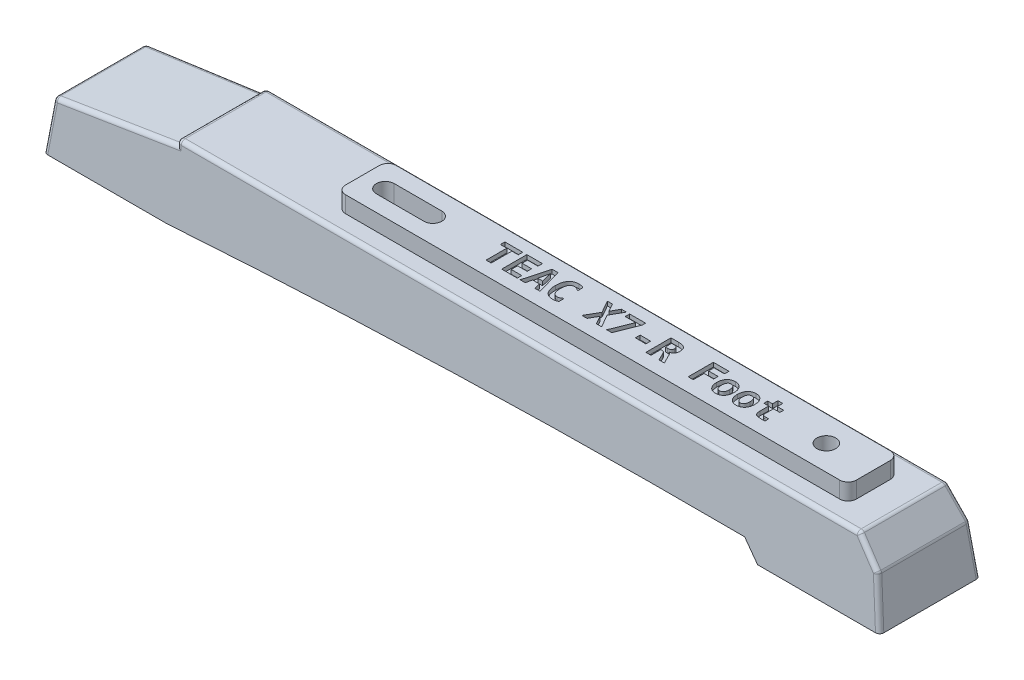
SolidWorks part; units mm, degrees
ref_plane "Front Plane" through (0, 0, 0) normal (0, 0, 1) x (1, 0, 0)
ref_plane "Top Plane" through (0, 0, 0) normal (0, 1, 0) x (1, 0, 0)
ref_plane "Right Plane" through (0, 0, 0) normal (1, 0, 0) x (0, 0, -1)
sketch "Sketch1" plane through (0, 0, 0) normal (0, 1, 0) x (1, 0, 0)
  line L0 (-116.43, -6.1009) -> (-105.07, -6.1009) construction
  line L1 (-2, 0) -> (-119.93, 0)
  line L2 (0, -2) -> (0, -10.09)
  line L3 (-2, -12.09) -> (-119.93, -12.09)
  line L4 (-121.93, -2) -> (-121.93, -10.09)
  line L5 (-116.43, -3.9759) -> (-105.07, -3.9759)
  line L6 (-116.43, -8.2259) -> (-105.07, -8.2259)
  line L8 (-6.38, -2.95) -> (-2.48, -2.95)
  line L9 (-6.38, -2.95) -> (-6.38, -9.14)
  line L10 (-6.38, -9.14) -> (-2.48, -9.14)
  line L11 (-2.48, -2.95) -> (-2.48, -9.14)
  line L12 (-118.88, -1.42) -> (-102.67, -1.42)
  line L13 (-118.88, -1.42) -> (-118.88, -2.6)
  line L14 (-118.88, -2.6) -> (-102.67, -2.6)
  line L15 (-102.67, -1.42) -> (-102.67, -2.6)
  line L16 (-118.88, -9.52) -> (-102.67, -9.52)
  line L17 (-118.88, -9.52) -> (-118.88, -10.7)
  line L18 (-118.88, -10.7) -> (-102.67, -10.7)
  line L19 (-102.67, -9.52) -> (-102.67, -10.7)
  circle A0 centre (-11.18, -6.1009) radius 2.235
  arc A1 (-116.43, -3.9759) -> (-116.43, -8.2259) centre (-116.43, -6.1009) ccw
  arc A2 (-105.07, -8.2259) -> (-105.07, -3.9759) centre (-105.07, -6.1009) ccw
  arc A3 (-119.93, -12.09) -> (-121.93, -10.09) centre (-119.93, -10.09) cw
  arc A4 (-119.93, 0) -> (-121.93, -2) centre (-119.93, -2) ccw
  arc A5 (0, -10.09) -> (-2, -12.09) centre (-2, -10.09) cw
  arc A6 (-2, 0) -> (0, -2) centre (-2, -2) cw
  point P9 (-110.75, -6.1009)
  point P22 (-121.93, 0)
  point P25 (0, -12.09)
  point P28 (0, 0)
  dimension "D3" = 6.1009
  dimension "D4" = 5.5
  dimension "D9" = 4.47
  dimension "D11" = 2
  dimension "D13" = 11.36
  dimension "D1" = 12.09
  dimension "D2" = 121.93
  dimension "D5" = 11.18
  dimension "D6" = 3.9
  dimension "D7" = 6.19
  dimension "D8" = 2.95
  dimension "D10" = 2.48
  dimension "D12" = 4.25
  dimension "D14" = 1.18
  dimension "D15" = 1.18
  dimension "D16" = 1.39
  dimension "D17" = 1.42
  dimension "D18" = 3.05
  dimension "D19" = 3.05
  dimension "D20" = 16.21
extrude "Boss-Extrude1" add sketch "Sketch1" along normal blind 3.93 contours L15 L12 L13 L14 | A6 L1 A4 L4 A3 L3 A5 L2 A2 L6 A1 L5 A0 L8 L11 L10 L9 L12 L15 L14 L13 L16 L19 L18 L17 | L19 L16 L17 L18 | L11 L8 L9 L10 region at (-58.8079, 0, 6.0413) region at (-4.43, 0, 6.045) region at (-110.775, 0, 2.01) region at (-110.775, 0, 10.11)
sketch "Sketch2" plane through (0, 0, 0) normal (0, -1, 0) x (1, 0, 0)
  line L0 (-2, 0) -> (-119.93, 0) construction
  line L1 (13.52, 18.07) -> (-186.01, 18.07)
  line L2 (13.52, 18.07) -> (13.52, -5.98)
  line L3 (13.52, -5.98) -> (-186.01, -5.98)
  line L4 (-186.01, 18.07) -> (-186.01, -5.98)
  line L5 (0, 2) -> (0, 10.09) construction
  line L6 (-121.93, 2) -> (-121.93, 10.09) construction
  dimension "D1" = 24.05
  dimension "D2" = 5.98
  dimension "D3" = 13.52
  dimension "D4" = 64.08
extrude "Boss-Extrude2" add sketch "Sketch2" along normal blind 17.4
sketch "Sketch3" plane through (0, 0, 18.07) normal (0, 0, 1) x (1, 0, 0)
  line L0 (13.52, -17.4) -> (12.04, -5.98)
  line L1 (12.04, -5.98) -> (7.2, 0)
  line L2 (13.52, 0) -> (-186.01, 0) construction
  line L3 (7.2, 0) -> (13.52, 0)
  line L4 (13.52, 0) -> (13.52, -17.4)
  line L5 (13.52, -17.4) -> (-186.01, -17.4) construction
  line L6 (0, 3.93) -> (0, 0) construction
  dimension "D1" = 11.42
  dimension "D2" = 7.2
  dimension "D3" = 1.48
extrude "Cut-Extrude1" cut sketch "Sketch3" against normal through all
sketch "Sketch5" plane through (0, 0, 18.07) normal (0, 0, 1) x (1, 0, 0)
  line L0 (-186.01, -17.4) -> (-184.53, -5.64)
  line L1 (-184.53, -5.64) -> (-155.57, -1.26)
  line L2 (-186.01, -17.4) -> (-186.01, 0)
  line L3 (-186.01, 0) -> (-155.57, 0)
  line L4 (7.2, 0) -> (-186.01, 0) construction
  line L5 (-155.57, 0) -> (-155.57, -1.26)
  line L6 (13.52, -17.4) -> (-186.01, -17.4) construction
  line L7 (-121.93, 3.93) -> (-121.93, 0) construction
  dimension "D1" = 11.76
  dimension "D2" = 1.48
  dimension "D3" = 33.64
  dimension "D4" = 1.26
extrude "Cut-Extrude2" cut sketch "Sketch5" against normal through all
sketch "Sketch6" plane through (0, 0, 18.07) normal (0, 0, 1) x (1, 0, 0)
  line L0 (-15.6, -17.4) -> (-19.0304, -13.5)
  line L1 (13.52, -17.4) -> (-186.01, -17.4) construction
  line L2 (-15.6, -17.4) -> (-156.64, -17.4)
  spline S0 degree 2 poles (-156.64, -17.4) (-87.929, -13.1135) (-19.0304, -13.5) knots 0 0 0 1 1 1
  point P6 (-135.5295, -16.1935)
  dimension "D1" = 29.37
  dimension "D2" = 29.12
  dimension "D3" = 3.9
extrude "Cut-Extrude3" cut sketch "Sketch6" against normal through all
sketch3d "3DSketch2"
  line L0 (0, 0, 16.59) -> (0, -17.4, 18.07)
  line L1 (0, 0, 18.07) -> (0, 0, 16.59)
  line L2 (7.2, 0, 18.07) -> (-155.57, 0, 18.07) construction
  line L3 (13.52, -17.4, 18.07) -> (-15.6, -17.4, 18.07) construction
  line L4 (0, -17.4, 18.07) -> (0, 0, 18.07)
  line L5 (0, 0, -5.98) -> (0, 0, -4.5)
  line L6 (-155.57, 0, -5.98) -> (7.2, 0, -5.98) construction
  line L7 (0, 0, -4.5) -> (0, -17.4, -5.98)
  line L8 (0, -17.4, -5.98) -> (0, 0, -5.98)
  point P12 (0, 0, 0)
  point P13 (0, 0, 0)
  dimension "D1" = 1.48
  dimension "D2" = 1.48
extrude "Cut-Extrude4" cut sketch "3DSketch2" along direction (1, 0, 0) on the side of the normal through all and the other way through all
extrude "Cut-Extrude5" cut sketch "Sketch1<3>" against normal blind 17.4 contours L6 A2 L5 A1 | A0 region at (-110.75, 0, 6.1009) region at (-11.18, 0, 6.1009)
sketch "Sketch1<3>" plane through (0, 0, 0) normal (0, 1, 0) x (1, 0, 0) same geometry as "Sketch1"
sketch "Sketch11" plane through (0, 3.93, 0) normal (0, 1, 0) x (1, 0, 0)
  line L15 (-105.07, -1.4059) -> (-116.43, -1.4059)
  line L16 (-116.43, -10.7959) -> (-105.07, -10.7959)
  line L17 (-105.07, -1.4059) -> (-116.43, -1.4059)
  line L18 (-116.43, -10.7959) -> (-105.07, -10.7959)
  arc A24 (-105.07, -10.7959) -> (-105.07, -1.4059) centre (-105.07, -6.1009) ccw
  arc A25 (-116.43, -1.4059) -> (-116.43, -10.7959) centre (-116.43, -6.1009) ccw
  arc A26 (-105.07, -10.7959) -> (-105.07, -1.4059) centre (-105.07, -6.1009) ccw
  arc A27 (-116.43, -1.4059) -> (-116.43, -10.7959) centre (-116.43, -6.1009) ccw
  circle A28 centre (-11.18, -6.1009) radius 4.805
  circle A29 centre (-11.18, -6.1009) radius 4.805
  dimension "D1" = 2.57
  dimension "D2" = 2.57
extrude "Cut-Extrude6" cut sketch "Sketch11" against normal up to next from offset 10.05 offset against normal yes
fillet "Fillet1" radius 1 5 edges at (-170.05, -3.45, 16.8834) (-170.05, -3.45, -4.7934) (-184.53, -5.64, 6.045)
fillet "Fillet2" radius 1 11 edges at (12.04, -5.98, 6.045) (9.62, -2.99, -4.7543) (9.62, -2.99, 16.8443) (7.2, 0, 6.045) (-155.57, 0, 6.045) (-155.57, -1.0933, 16.683) (-155.57, -1.0933, -4.593)
sketch "Sketch12" plane through (0, 3.93, 0) normal (0, 1, 0) x (1, 0, 0)
  text T0 "TEAC X7-R Foot" font "DejaVu Sans Mono" height 6
extrude "Cut-Extrude7" cut sketch "Sketch12" against normal blind 1
